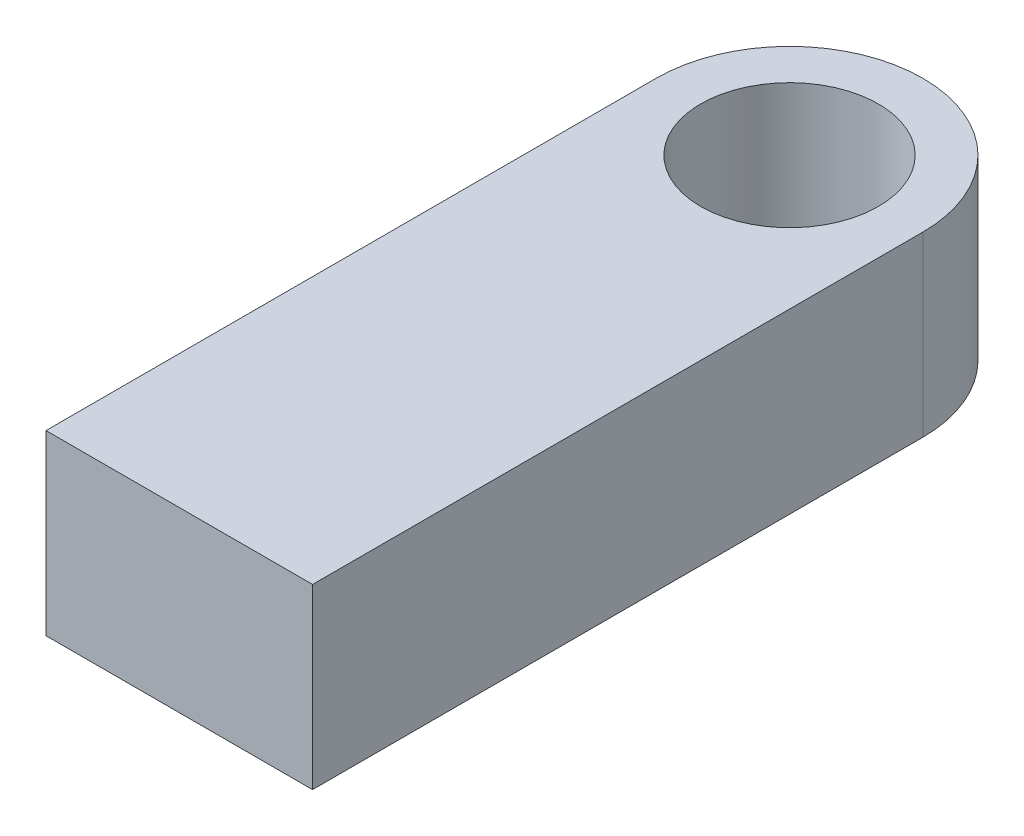
SolidWorks part; units mm, degrees
ref_plane "Front Plane" through (0, 0, 0) normal (0, 0, 1) x (1, 0, 0)
ref_plane "Top Plane" through (0, 0, 0) normal (0, 1, 0) x (1, 0, 0)
ref_plane "Right Plane" through (0, 0, 0) normal (1, 0, 0) x (0, 0, -1)
sketch "Sketch1" plane through (0, 0, 0) normal (0, 1, 0) x (1, 0, 0)
  line L1 (-15, 0) -> (-15, -68.6799)
  line L2 (15, 0) -> (15, -68.6799)
  line L3 (-15, -68.6799) -> (15, -68.6799)
  circle A0 centre (0, 0) radius 10
  arc A1 (15, 0) -> (-15, 0) centre (0, 0) ccw
  dimension "D1" = 20
extrude "Boss-Extrude1" add sketch "Sketch1" along normal blind 20
